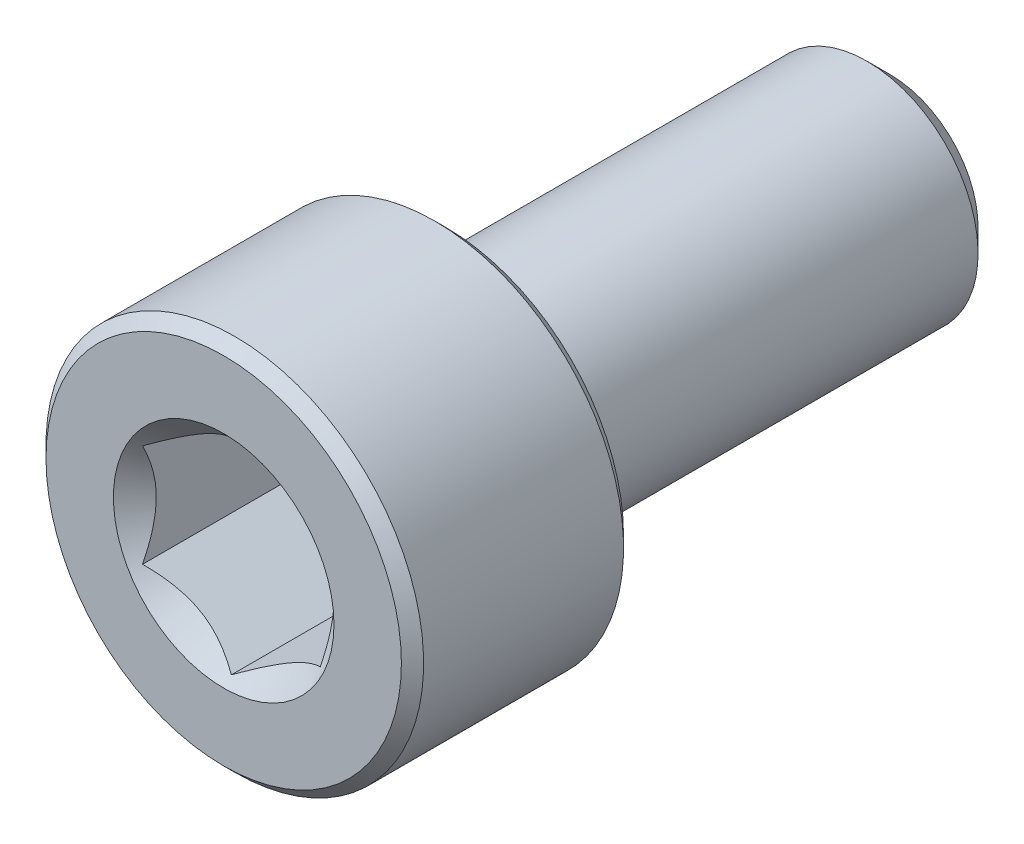
SolidWorks part; units mm, degrees
ref_plane "Front Plane" through (0, 0, 0) normal (0, 0, 1) x (1, 0, 0)
ref_plane "Top Plane" through (0, 0, 0) normal (0, 1, 0) x (1, 0, 0)
ref_plane "Right Plane" through (0, 0, 0) normal (1, 0, 0) x (0, 0, -1)
sketch "Sketch1" plane through (0, 0, 0) normal (1, 0, 0) x (0, 0, -1)
  line L0 (-7.5, 0) -> (7.5, 0) construction
  line L1 (7.5, 0) -> (7.5, 1.9804) construction
  line L2 (7.5, 1.9804) -> (6.9804, 2.5) construction
  line L3 (6.9804, 2.5) -> (6.9, 2.5) construction
  line L4 (6.9, 2.5) -> (-2.5, 2.5) construction
  line L5 (-2.5, 2.5) -> (-2.5, 4.25) construction
  line L6 (-2.5, 4.25) -> (-7.5, 4.25) construction
  line L7 (-7.5, 4.25) -> (-7.5, 0) construction
  line L8 (7.5, 1.9804) -> (7.5, 2.5) construction
  line L9 (7.45, 2.5866) -> (7.85, 1.8938) construction
  line L10 (7.85, 1.8938) -> (8.25, 2.5866) construction
  line L11 (8.25, 2.5866) -> (7.45, 2.5866) construction
  line L12 (7.85, 2.5866) -> (7.85, 2.5) construction
  line L13 (7.85, 1.8938) -> (7.85, 1.9804) construction
  line L14 (7.8, 1.9804) -> (7.9, 1.9804) construction
  line L15 (7.5, 2.5) -> (8.2, 2.5) construction
  line L16 (7.475, 2.5433) -> (8.225, 2.5433) construction
  line L17 (7.5, 0) -> (7.5, -2.5) construction
  line L18 (-2.75, 4.25) -> (-2.5, 4) construction
  line L19 (-7.25, 4.25) -> (-7.5, 4) construction
  line L20 (-2.5, 2.5) -> (-2.5, 0) construction
  line L21 (-2.5, 1.25) -> (0.8333, 1.25) construction
  line L22 (0.8333, 1.25) -> (4.1667, 1.25) construction
  line L23 (4.1667, 1.25) -> (7.5, 1.25) construction
  line L24 (0.8333, 1.25) -> (0.8333, 2.5) construction
  line L25 (0.8333, 2.5) -> (0.8333, 4.25) construction
  line L26 (4.1667, 1.25) -> (4.1667, 4.25) construction
  point P0 (-7.5, 2)
  point P3 (5.5, 2.5)
  point P4 (0, 0)
  point P18 (4.1667, 2.5)
  point P22 (7.85, 1.9804)
  point P24 (6.9, 2.5)
  point P25 (7.85, 2.5)
  point P28 (7.85, 2.5433)
  point P29 (5.5, -2.5)
  point P30 (0.8333, 2.5)
  point P31 (-5, 4.25)
  point P37 (-3.375, 4.25)
  point P38 (-7.125, 4.25)
  point P45 (0.8333, 1.25)
  point P46 (4.1667, 1.25)
  dimension "D2" = 0.1
  dimension "D7" = 0.25
  dimension "D8" = 0.25
  dimension "D9" = 0.25
  dimension "D10" = 0.125
  dimension "D11" = 0.625
  dimension "Drive Size" = 4
  dimension "Head Diameter" = 8.5
  dimension "Head Height" = 5
  dimension "Thread Pitch" = 0.8
  dimension "Thread Dia" = 5
  dimension "Length" = 10
  dimension "D12" = 0.6
  dimension "D4" = 2
  dimension "D3" = 45
sketch "Sketch2" plane through (0, 0, 0) normal (1, 0, 0) x (0, 0, -1)
  line L0 (-7.5, 0) -> (-7.5, 4)
  line L1 (-7.25, 4.25) -> (-2.75, 4.25)
  line L2 (-2.5, 4) -> (-2.5, 2.75)
  line L4 (6.9804, 2.5) -> (7.5, 1.9804)
  line L5 (7.5, 1.9804) -> (7.5, 0)
  line L6 (-2.5, 4.25) -> (-7.5, 4.25) construction
  line L7 (7.5, 0) -> (-7.5, 0)
  line L8 (-7.25, 4.25) -> (-7.5, 4) construction
  line L10 (-7.25, 4.25) -> (-7.5, 4)
  line L14 (-2.75, 4.25) -> (-2.5, 4) construction
  line L16 (-2.75, 4.25) -> (-2.5, 4)
  line L17 (-2.5, 2.5) -> (-2.5, 4.25) construction
  line L19 (-2.25, 2.5) -> (6.9804, 2.5)
  line L20 (6.9, 2.5) -> (-2.5, 2.5) construction
  arc A1 (-2.5, 2.75) -> (-2.25, 2.5) centre (-2.25, 2.75) ccw
  dimension "D3" = 0.25
revolve "Revolve1" add sketch "Sketch2" angle 360 about L7
sketch "Sketch3" plane through (0, 0, 7.5) normal (0, 0, 1) x (1, 0, 0)
  line L1 (2, -1.1547) -> (2, 1.1547)
  line L2 (2, 1.1547) -> (0, 2.3094)
  line L3 (0, 2.3094) -> (-2, 1.1547)
  line L4 (-2, 1.1547) -> (-2, -1.1547)
  line L5 (-2, -1.1547) -> (0, -2.3094)
  line L6 (0, -2.3094) -> (2, -1.1547)
  circle A0 centre (0, 0) radius 2 construction
  circle A1 centre (0, 0) radius 4.25 construction
  circle A2 centre (0, 0) radius 4.25 construction
  circle A3 centre (0, 0) radius 2.3094 construction
  point P13 (0, 0)
  dimension "D1" = 4.6188
extrude "Cut-Extrude1" cut sketch "Sketch3" against normal offset from surface (4 mm away) 1 up to face at (0, 4, 2.5)
sketch "Sketch4" plane through (0, 0, 7.5) normal (0, 0, 1) x (1, 0, 0)
  circle A0 centre (0, 0) radius 2.4826
  dimension "D1" = 4.9652
extrude "Cut-Extrude2" cut sketch "Sketch4" against normal up to vertex (2.5 mm away) draft 45 up to point (0, 4.25, 5)
sketch "Sketch11" plane through (0, 0, 0) normal (1, 0, 0) x (0, 0, -1)
  line L0 (-7.5, 0) -> (7.5, 0) construction
  line L1 (-7.5, 0) -> (7.5, 0) construction
  line L2 (-0.625, 0) -> (-0.625, 2.5) construction
  line L3 (6.9, 2.5) -> (-2.5, 2.5) construction
  line L4 (5.625, 0) -> (5.625, 2.5) construction
  line L6 (7.5, 1.9804) -> (7.5, 2.5) construction
  point P2 (-0.625, 0)
  point P3 (5.625, 0)
  dimension "D1" = 1.875
  dimension "D2" = 1.875
sketch "Sketch6" [suppressed] plane through (0, 0, -7.5) normal (0, 0, -1) x (-1, 0, 0)
  circle A0 centre (0, 0) radius 2.5
curve "Helix/Spiral1" [suppressed] pitch 0.8 height 10.8 turns 13.5
sketch "Sketch10" [suppressed] plane through (0, 0, 0) normal (1, 0, 0) x (0, 0, -1)
  line L0 (-2.25, -4.25) -> (-2.25, 4.25)
  line L5 (-7.5, 0) -> (7.5, 0) construction
  line L6 (-2.25, 2.5) -> (-2.25, -2.5) construction
  point P3 (-2.25, 0)
split "Split1" [suppressed] bodies to split 106
sketch "Sketch7" [suppressed] plane through (0, 0, 0) normal (1, 0, 0) x (0, 0, -1)
  line L0 (7.475, 2.5433) -> (8.225, 2.5433)
  line L1 (8.225, 2.5433) -> (7.9, 1.9804)
  line L2 (7.9, 1.9804) -> (7.8, 1.9804)
  line L3 (7.8, 1.9804) -> (7.475, 2.5433)
sweep "Cut-Sweep1" [suppressed] cut profiles "Sketch7" path "Helix/Spiral1"
sketch "Sketch8" [suppressed] plane through (0, 0, 0) normal (1, 0, 0) x (0, 0, -1)
  line L0 (-2.5, 0) -> (-2.5, 2.5)
  line L1 (-2.25, -2.5) -> (-2.25, 2.5) construction
  line L2 (-2.5, 2.5) -> (-2.25, 2.5)
  line L4 (-2.25, 2.5) -> (-0.8066, 0)
  line L5 (-0.8066, 0) -> (-2.5, 0)
  line L6 (6.9, 2.5) -> (-2.5, 2.5) construction
  line L7 (-7.5, 0) -> (7.5, 0) construction
  dimension "D1" = 60
revolve "Revolve2" [suppressed] add sketch "Sketch8" angle 360 about L5
equation "\"D2@Sketch1\" = \"Thread Pitch@Sketch1\" / 8"
equation "\"D4@Helix/Spiral1\" = \"Thread Pitch@Sketch1\""
equation "\"D7@Sketch1\" = \"Head Height@Sketch1\" * .05"
equation "\"D8@Sketch1\"=\"D7@Sketch1\""
equation "\"D9@Sketch1\"=\"D7@Sketch1\""
equation "\"D10@Sketch1\"=\"D7@Sketch1\"/2"
equation "\"D11@Sketch1\"=\"D10@Sketch1\"*5"
equation "\"D4@Sketch1\"=\"Thread Pitch@Sketch1\"*2.5"
equation "\"D12@Sketch1\"=\"Thread Pitch@Sketch1\"*.75"
equation "\"D3@Helix/Spiral1\"=\"Length@Sketch1\"+\"Thread Pitch@Sketch1\""
equation "\"D3@Sketch2\"=\"Thread Dia@Sketch1\"*0.05"
equation "\"D1@Sketch11\"=\"Length@Sketch1\"*0.1875"
equation "\"D2@Sketch11\"=\"D1@Sketch11\""
equation "\"D1@Sketch4\"=\"D1@Sketch3\"*1.075"
